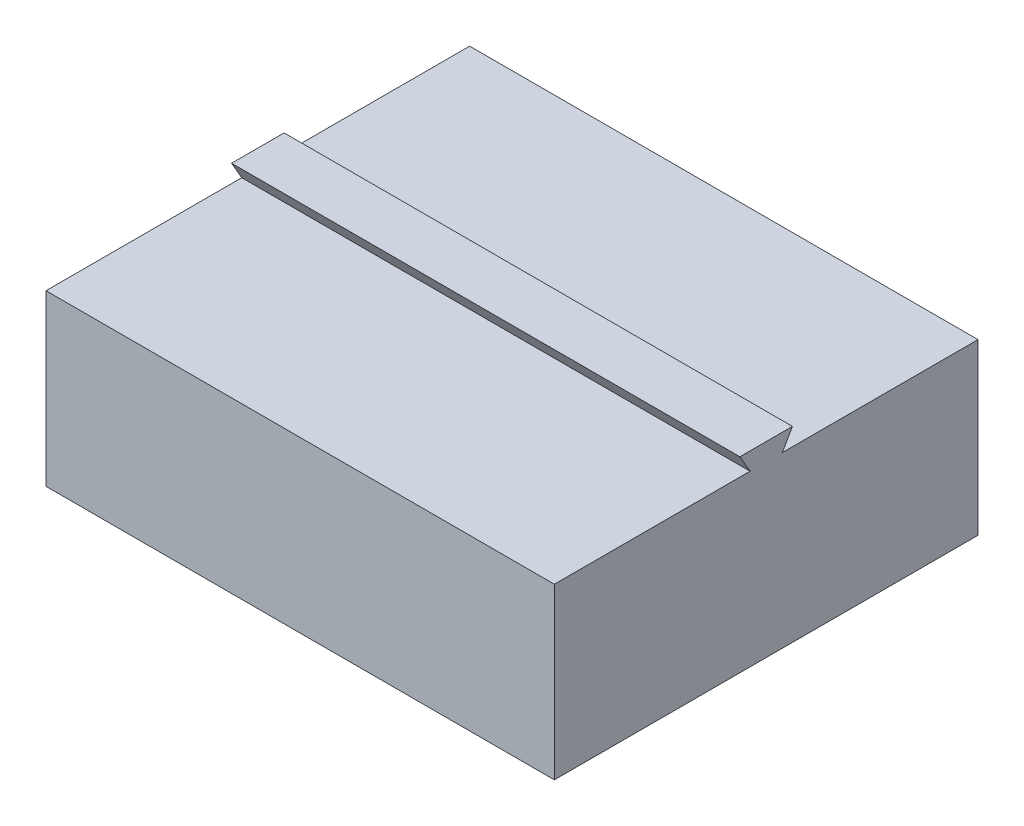
SolidWorks part; units mm, degrees
ref_plane "Front Plane" through (0, 0, 0) normal (0, 0, 1) x (1, 0, 0)
ref_plane "Top Plane" through (0, 0, 0) normal (0, 1, 0) x (1, 0, 0)
ref_plane "Right Plane" through (0, 0, 0) normal (1, 0, 0) x (0, 0, -1)
sketch "Sketch1" plane through (0, 0, 0) normal (0, 1, 0) x (1, 0, 0)
  line L1 (60, -50) -> (-60, -50)
  line L2 (60, -50) -> (60, 50)
  line L3 (60, 50) -> (-60, 50)
  line L4 (-60, -50) -> (-60, 50)
  line L5 (60, -50) -> (-60, 50) construction
  line L6 (60, 50) -> (-60, -50) construction
  point P0 (0, 0)
  dimension "D1" = 120
  dimension "D2" = 100
extrude "Boss-Extrude1" add sketch "Sketch1" along normal blind 40
sketch "Sketch2" plane through (60, 0, 0) normal (1, 0, 0) x (0, 0, -1)
  line L0 (-3.8, 40) -> (-6.2018, 44.16)
  line L1 (-50, 40) -> (50, 40) construction
  line L2 (-6.2018, 44.16) -> (6.2018, 44.16)
  line L3 (6.2018, 44.16) -> (3.8, 40)
  line L4 (3.8, 40) -> (-3.8, 40)
  line L5 (0, -1000) -> (0, 49000) construction
  dimension "D1" = 60
  dimension "D2" = 4.16
  dimension "D3" = 60
  dimension "D4" = 7.6
extrude "Boss-Extrude2" add sketch "Sketch2" against normal up to surface (120 mm away) up to face at (-60, 20, 0)
ref_point "Point1"
ref_axis "Axis1" through (0, 0, 0) along (0, 1, 0)
ref_point "Point2"
ref_axis "Axis2" through (-60, 20.229, 0) along (1, 0, 0)
ref_point "CM"
sketch "Sketch3" plane through (0, 0, 0) normal (0, -1, 0) x (1, 0, 0)
  line L0 (-60, 50) -> (60, 50) construction
  line L1 (56, -46) -> (-56, -46)
  line L2 (56, -46) -> (56, 46)
  line L3 (56, 46) -> (-56, 46)
  line L4 (-56, -46) -> (-56, 46)
  line L5 (56, -46) -> (-56, 46) construction
  line L6 (56, 46) -> (-56, -46) construction
  line L7 (60, 50) -> (60, -50) construction
  point P0 (0, 0)
  dimension "D1" = 4
  dimension "D2" = 4
sketch "Sketch5" plane through (0, 0, 0) normal (0, -1, 0) x (1, 0, 0)
  line L0 (-10.8887, -30.1351) -> (-10.8887, 13.3244)
  line L1 (-10.8887, 13.3244) -> (-25.4837, 13.3244)
  line L2 (-25.4837, 13.3244) -> (0, 40.5462)
  line L3 (0, 40.5462) -> (25.4837, 13.3244)
  line L4 (25.4837, 13.3244) -> (10.8887, 13.3244)
  line L5 (10.8887, 13.3244) -> (10.8887, -30.1351)
  line L6 (10.8887, -30.1351) -> (-10.8887, -30.1351)
  line L7 (0, -990.9816) -> (0, 49009.0184) construction
  line L8 (56, -46) -> (-56, 46) construction
  point P8 (0, 40.5462)
  point P12 (0, 0)
extrude "Cut-Extrude2" cut sketch "Sketch5" against normal blind 1
